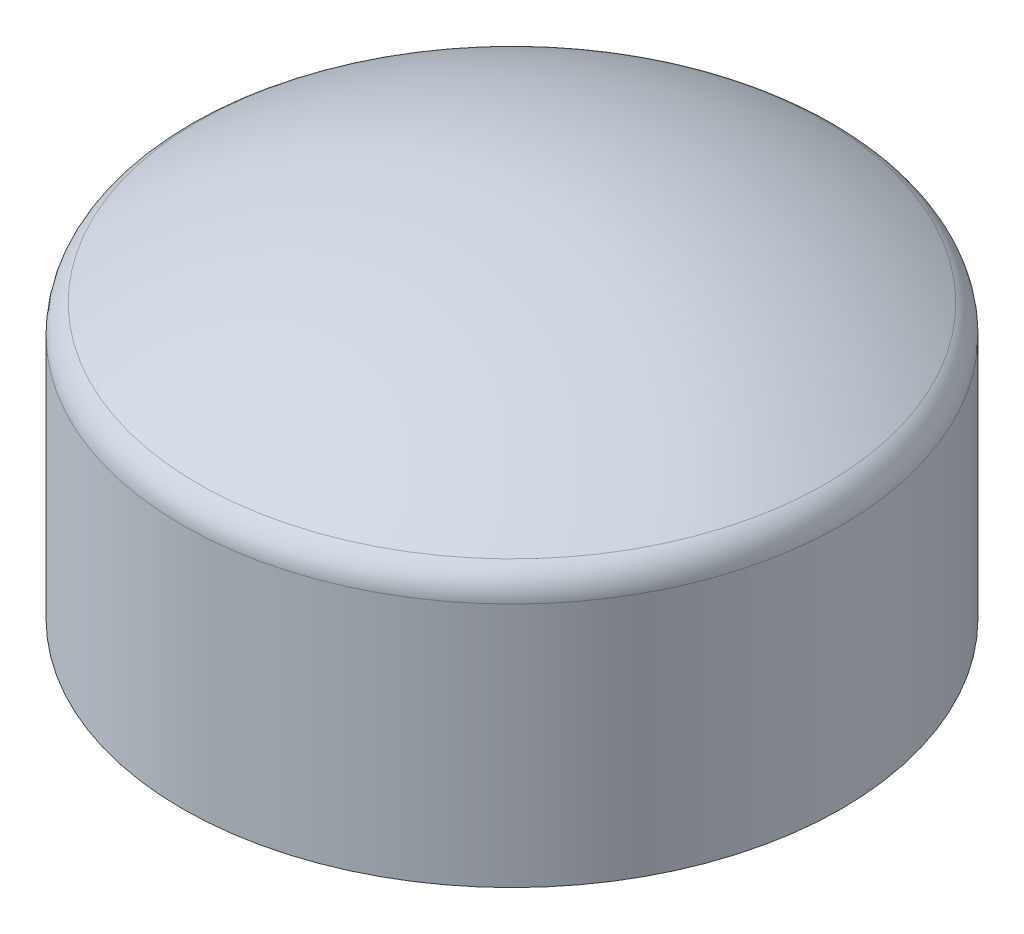
SolidWorks part; units mm, degrees
material "ABS"
ref_plane "Front Plane" through (0, 0, 0) normal (0, 0, 1) x (1, 0, 0)
ref_plane "Top Plane" through (0, 0, 0) normal (0, 1, 0) x (1, 0, 0)
ref_plane "Right Plane" through (0, 0, 0) normal (1, 0, 0) x (0, 0, -1)
sketch "Sketch1" plane through (0, 0, 0) normal (0, 0, 1) x (1, 0, 0)
  line L0 (-8, 0) -> (-10, 0)
  line L1 (-8, 0) -> (8, 0) construction
  line L2 (-8, 0) -> (-8, 7)
  line L3 (-8, 7) -> (0, 7)
  line L5 (-10, 0) -> (-10, 8)
  line L6 (0, 7) -> (0, 11)
  line L7 (0, 11) -> (0.8573, 11) construction
  arc A0 (-10, 8) -> (0, 11) centre (0, -7.1667) cw
  dimension "D3" = 2
  dimension "D1" = 7
  dimension "D2" = 16
  dimension "D4" = 4
  dimension "D5" = 1
revolve "Revolve1" add sketch "Sketch1" angle 360 about L6
fillet "Fillet1" radius 1 1 edges at (10, 8, 0)
